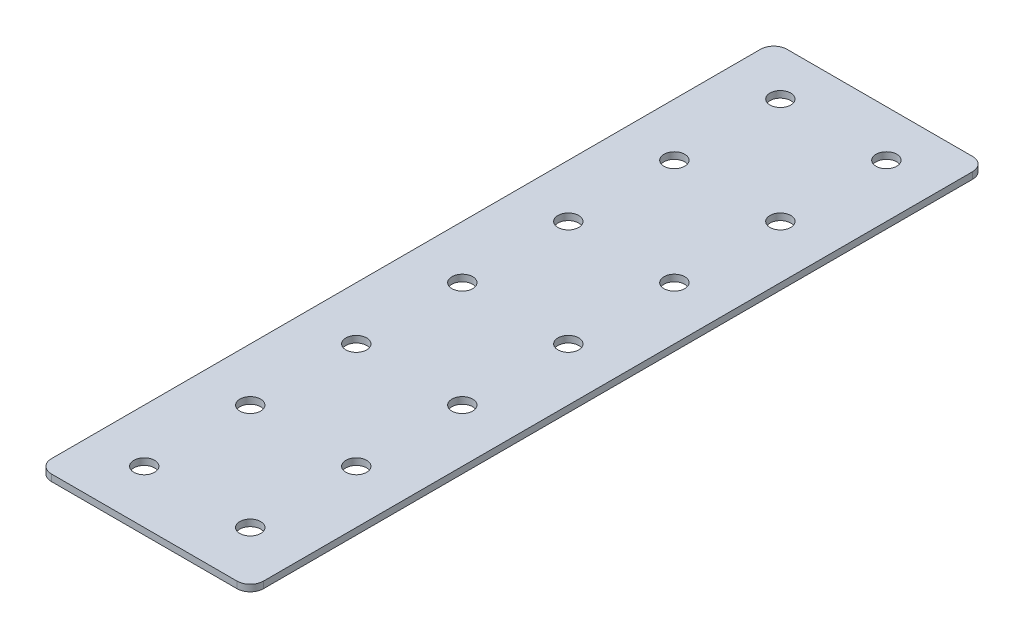
SolidWorks part; units mm, degrees
material "6061-T6 (SS)"
ref_plane "Front Plane" through (0, 0, 0) normal (0, 0, 1) x (1, 0, 0)
ref_plane "Top Plane" through (0, 0, 0) normal (0, 1, 0) x (1, 0, 0)
ref_plane "Right Plane" through (0, 0, 0) normal (1, 0, 0) x (0, 0, -1)
sketch "Sketch1" plane through (0, 0, 0) normal (0, 1, 0) x (1, 0, 0)
  line L1 (0, 0) -> (50.8, 0)
  line L2 (0, 0) -> (0, 176.2125)
  line L3 (0, 176.2125) -> (50.8, 176.2125)
  line L4 (50.8, 0) -> (50.8, 176.2125)
  circle A0 centre (12.7, 12.7) radius 2.4892
  circle A1 centre (12.7, 38.1) radius 2.4892
  circle A2 centre (12.7, 63.5) radius 2.4892
  circle A3 centre (12.7, 88.9) radius 2.4892
  circle A4 centre (12.7, 114.3) radius 2.4892
  circle A5 centre (12.7, 139.7) radius 2.4892
  circle A6 centre (38.1, 38.1) radius 2.4892
  circle A7 centre (38.1, 63.5) radius 2.4892
  circle A8 centre (38.1, 88.9) radius 2.4892
  circle A9 centre (38.1, 114.3) radius 2.4892
  circle A10 centre (38.1, 139.7) radius 2.4892
  circle A11 centre (38.1, 12.7) radius 2.4892
  circle A12 centre (12.7, 165.1) radius 2.4892
  circle A14 centre (38.1, 165.1) radius 2.4892
  circle A16 centre (12.7, 190.5) radius 2.4892 [skipped]
  circle A17 centre (38.1, 190.5) radius 2.4892 [skipped]
  dimension "D3" = 4.9784
  dimension "D4" = 12.7
  dimension "D5" = 12.7
  dimension "D1" = 50.8
  dimension "D2" = 176.2125
  dimension "D8" = 25.4
  dimension "D9" = 25.4
  dimension "D6" = 8
  dimension "D7" = 2
extrude "Boss-Extrude1" add sketch "Sketch1" along normal blind 1.5875
fillet "Fillet1" radius 3.175 4 edges at (0, 0.7937, -176.2125) (50.8, 0.7937, -176.2125) (0, 0.7937, 0) (50.8, 0.7937, 0)
